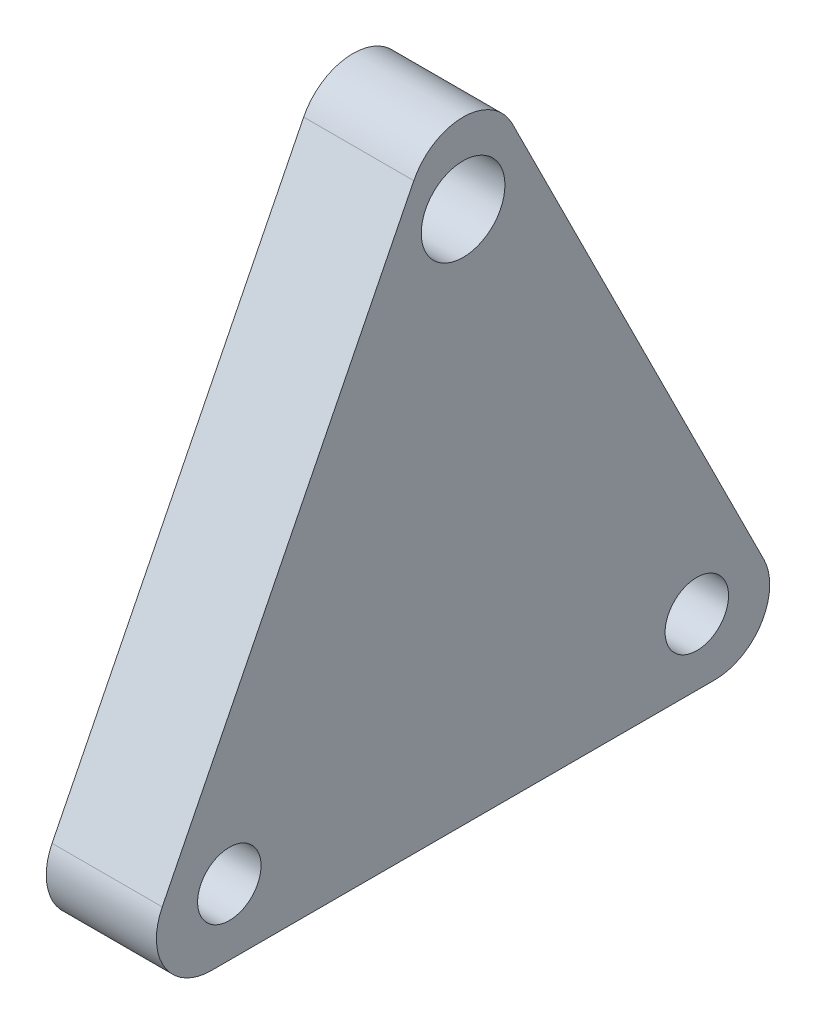
SolidWorks part; units mm, degrees
ref_plane "Front Plane" through (0, 0, 0) normal (0, 0, 1) x (1, 0, 0)
ref_plane "Top Plane" through (0, 0, 0) normal (0, 1, 0) x (1, 0, 0)
ref_plane "Right Plane" through (0, 0, 0) normal (1, 0, 0) x (0, 0, -1)
sketch "Sketch1" plane through (0, 0, 0) normal (1, 0, 0) x (0, 0, -1)
  line L0 (-13.4747, 0) -> (13.4747, 0) construction
  line L1 (0, 0) -> (0, 26.9494) construction
  line L2 (-13.4747, 0) -> (0, 26.9494) construction
  line L3 (0, 26.9494) -> (13.4747, 0) construction
  line L4 (13.4747, 0) -> (-13.4747, 0) construction
  line L5 (19.6394, -3.81) -> (-19.6394, -3.81)
  line L6 (-19.6394, -3.81) -> (0, 35.4688)
  line L7 (0, 35.4688) -> (19.6394, -3.81)
  circle A0 centre (-13.4747, 0) radius 1.8288
  circle A1 centre (0, 26.9494) radius 2.413
  circle A2 centre (13.4747, 0) radius 1.8288
  point P4 (0, 0)
  dimension "D3" = 3.6576
  dimension "D4" = 4.826
  dimension "D1" = 26.9494
  dimension "D2" = 3.81
extrude "Boss-Extrude1" add sketch "Sketch1" along normal blind 6.35
fillet "Fillet1" radius 3.175 3 edges at (3.175, 35.4688, 0) (3.175, -3.81, -19.6394) (3.175, -3.81, 19.6394)
